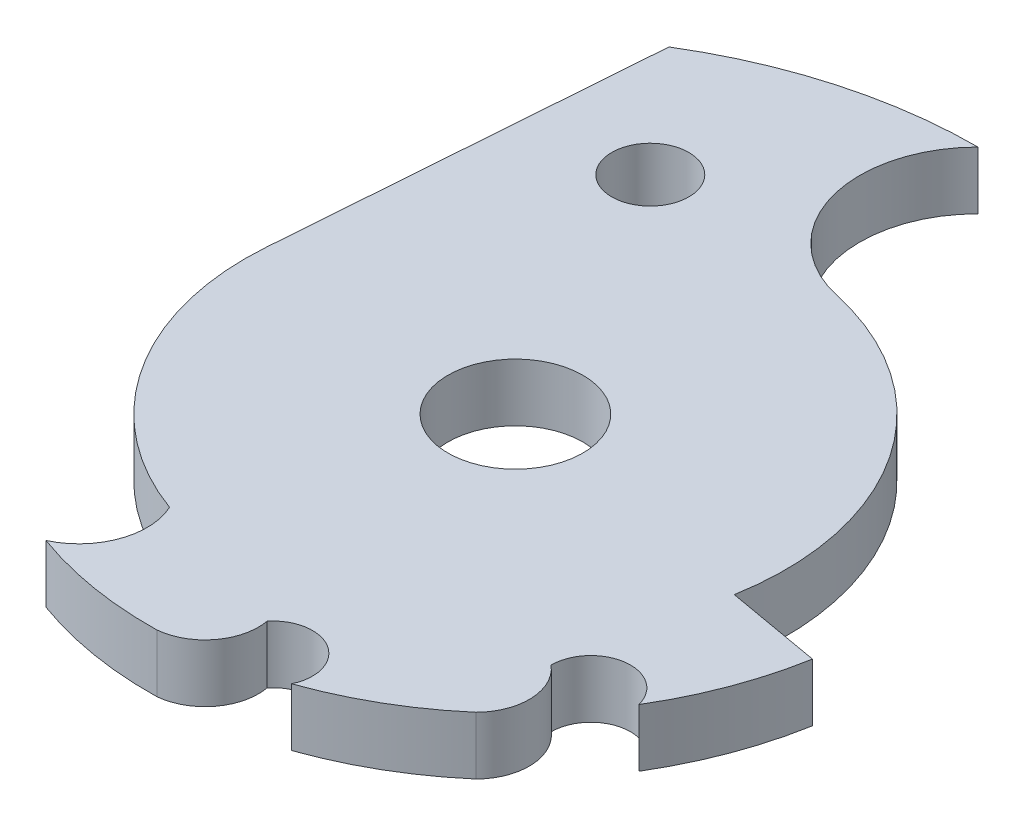
SolidWorks part; units mm, degrees
material "AISI Type A2 Tool Steel"
ref_plane "Front Plane" through (0, 0, 0) normal (0, 0, 1) x (1, 0, 0)
ref_plane "Top Plane" through (0, 0, 0) normal (0, 1, 0) x (1, 0, 0)
ref_plane "Right Plane" through (0, 0, 0) normal (1, 0, 0) x (0, 0, -1)
other "Center of Mass"
other "Bounding Box"
ref_plane "Default Plane" through (-8.9266, -12.7485, 0) normal (-0.1736, 0.9848, 0) x (0.9848, 0.1736, 0)
sketch "Sketch1" plane through (0, 0, 0) normal (0, 1, 0) x (1, 0, 0)
  circle A0 centre (0, 0) radius 76.2 construction
  circle A1 centre (0, 0) radius 44.45
  circle A2 centre (0, 0) radius 11.1125
  dimension "D1" = 22.225
  dimension "D2" = 88.9
  dimension "D3" = 152.4
extrude "Boss-Extrude1" add sketch "Sketch1" along normal mid plane 9.525
sketch "Sketch2" plane through (0, 4.7625, 0) normal (0, 1, 0) x (1, 0, 0)
  line L0 (-44.3273, 3.3) -> (-39.7324, 65.0214)
  line L1 (0, 0) -> (0, 76.2) construction
  line L2 (0, 0) -> (0, 76.2) construction
  line L3 (0, 76.2) -> (-76.2, 0) construction
  line L4 (-39.7324, 65.0214) -> (0, 76.2) construction
  circle A0 centre (0, 0) radius 44.45 construction
  circle A1 centre (0, 0) radius 76.2 construction
  arc A2 (-39.7324, 65.0214) -> (0, 76.2) centre (0, 0) cw
  arc A3 (0, 76.2) -> (9.5766, 43.4061) centre (13.7731, 62.4269) ccw
  arc A4 (-44.3273, 3.3) -> (9.5766, 43.4061) centre (0, 0) cw
  dimension "D1" = 45
  dimension "D2" = 41.275
extrude "Boss-Extrude2" add sketch "Sketch2" against normal through all
sketch "Sketch3" plane through (0, 4.7625, 0) normal (0, 1, 0) x (1, 0, 0)
  line L0 (0, 0) -> (0, 76.2) construction
  line L1 (0, 0) -> (38.1, -65.9911) construction
  line L2 (-15.2028, -41.7693) -> (0, 0) construction
  line L3 (0, 0) -> (43.7747, -7.7187) construction
  line L4 (43.7747, -7.7187) -> (59.4085, -10.4753)
  line L5 (-20.6324, -56.687) -> (-15.2028, -41.7693)
  line L6 (0, 0) -> (-38.1, 65.9911) construction
  circle A0 centre (0, 0) radius 76.2 construction
  circle A1 centre (0, 0) radius 44.45 construction
  arc A2 (59.4085, -10.4753) -> (-20.6324, -56.687) centre (0, 0) cw
  arc A3 (-15.2028, -41.7693) -> (43.7747, -7.7187) centre (0, 0) ccw
  point P13 (30.1625, -52.243)
  arc M8 (-44.3273, 3.3) -> (9.5766, 43.4061) centre (0, 0) ccw
  dimension "D3" = 15.875
  dimension "D1" = 30
  dimension "D2" = 50
extrude "Boss-Extrude3" add sketch "Sketch3" against normal through all contours A2 L4 L5 M8 region at (23.1694, 4.7625, 40.1306)
sketch "Sketch4" plane through (0, 4.7625, 0) normal (0, 1, 0) x (1, 0, 0)
  line L0 (-34.5752, 67.9043) -> (0, 0) construction
  line L1 (-41.9181, 35.6625) -> (-23.0501, 45.2695) construction
  line L2 (-39.7324, 65.0214) -> (-44.3273, 3.3) construction
  line L3 (-23.0501, 45.2695) -> (-4.1822, 54.8766) construction
  circle A0 centre (-23.0501, 45.2695) radius 6.35
  circle A1 centre (0, 0) radius 44.45 construction
  arc A2 (0, 76.2) -> (9.5766, 43.4061) centre (13.7731, 62.4269) ccw construction
  circle A3 centre (0, 0) radius 76.2 construction
  dimension "D1" = 12.7
extrude "Cut-Extrude1" cut sketch "Sketch4" against normal through all
sketch "Sketch7" plane through (0, 4.7625, 0) normal (0, 1, 0) x (1, 0, 0)
  line L1 (9.0876, -49.9806) -> (0, 0) construction
  line L2 (0, 0) -> (38.7406, -32.8604) construction
  line L3 (-20.6324, -56.687) -> (1.2848, -60.3113) construction
  line L4 (20.0275, -56.9035) -> (39.2661, -45.7961) construction
  line L5 (51.5887, -31.2683) -> (59.4085, -10.4753) construction
  line L6 (1.2848, -60.3113) -> (20.0275, -56.9035) construction
  line L7 (39.2661, -45.7961) -> (51.5887, -31.2683) construction
  line L8 (0, 0) -> (-20.6324, -56.687) construction
  line L9 (-20.6324, -56.687) -> (75.2532, -11.9748) construction
  line L10 (0, 0) -> (20.0275, -56.9035) construction
  line L11 (20.0275, -56.9035) -> (65.7583, 38.5005) construction
  line L12 (9.0876, -49.9806) -> (38.7406, -32.8604) construction
  line L13 (30.1625, -52.243) -> (23.9141, -41.4205) construction
  arc A0 (-15.2028, -41.7693) -> (-20.6324, -56.687) centre (-25.3764, -46.5134) cw
  arc A1 (-20.6324, -56.687) -> (1.2848, -60.3113) centre (0, 0) ccw
  arc A2 (9.0876, -49.9806) -> (20.0275, -56.9035) centre (14.1499, -54.0861) cw
  arc A3 (-20.6324, -56.687) -> (59.4085, -10.4753) centre (0, 0) ccw construction
  arc A4 (1.2848, -60.3113) -> (9.0876, -49.9806) centre (0.4312, -51.5545) ccw
  arc A5 (38.7406, -32.8604) -> (51.5887, -31.2683) centre (45.2584, -32.8208) cw
  arc A6 (20.0275, -56.9035) -> (39.2661, -45.7961) centre (0, 0) ccw
  arc A7 (39.2661, -45.7961) -> (38.7406, -32.8604) centre (33.0494, -39.5701) ccw
  arc A8 (51.5887, -31.2683) -> (59.4085, -10.4753) centre (0, 0) ccw construction
  circle A9 centre (0, 0) radius 44.45 construction
  circle A10 centre (0, 0) radius 76.2 construction
  arc A11 (-15.2028, -41.7693) -> (51.5887, -31.2683) centre (57.2915, -285.2043) ccw
  point P22 (7.9516, -43.733)
  dimension "D5" = 254
  dimension "D1" = 6.35
  dimension "D2" = 45
  dimension "D3" = 45
  dimension "D4" = 19.05
extrude "Cut-Extrude2" cut sketch "Sketch7" against normal through all
